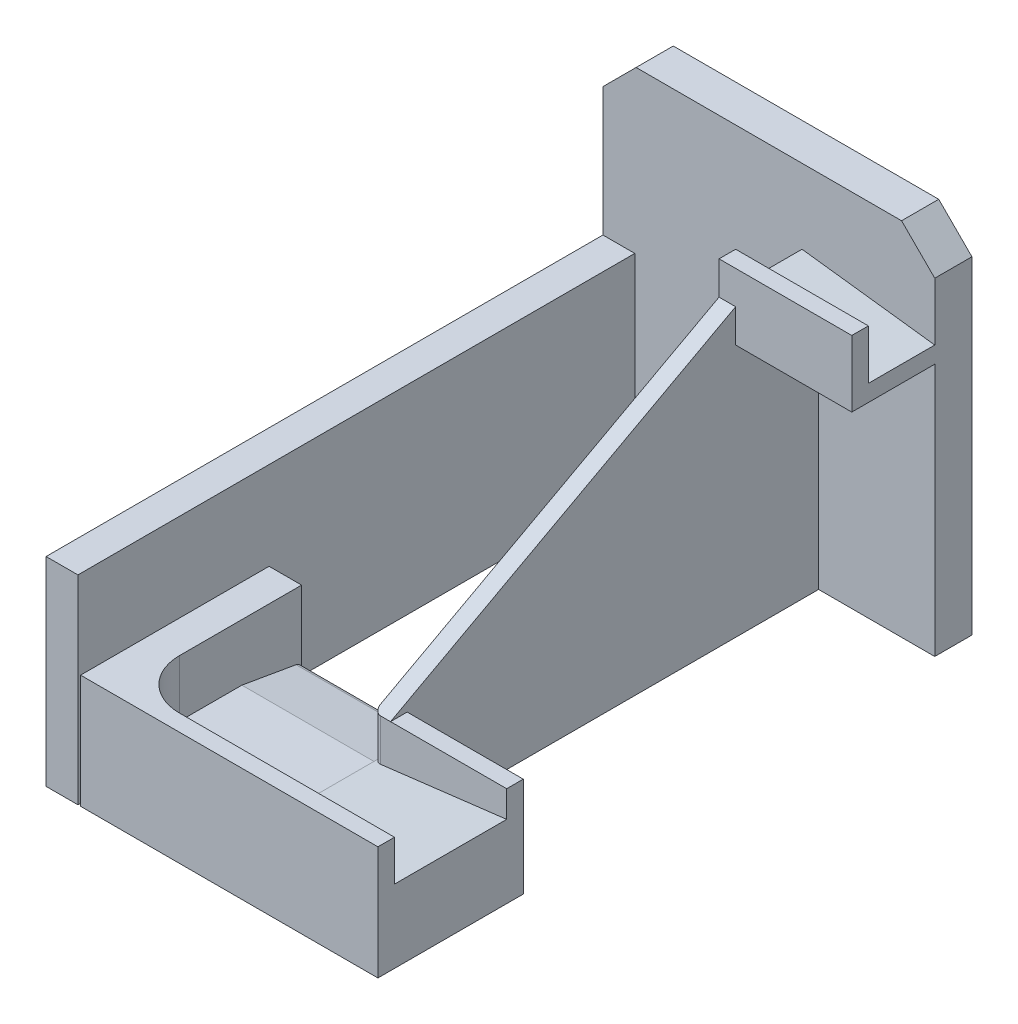
SolidWorks part; units mm, degrees
ref_plane "前视基准面" through (0, 0, 0) normal (0, 0, 1) x (1, 0, 0)
ref_plane "上视基准面" through (0, 0, 0) normal (0, 1, 0) x (1, 0, 0)
ref_plane "右视基准面" through (0, 0, 0) normal (1, 0, 0) x (0, 0, -1)
sketch "草图1" plane through (0, 0, 0) normal (0, 0, 1) x (1, 0, 0)
  line L0 (0, 49.365) -> (5, 54.365)
  line L1 (0, 0) -> (50, 0)
  line L2 (0, 0) -> (0, 49.365)
  line L3 (5, 54.365) -> (45, 54.365)
  line L4 (50, 0) -> (50, 49.365)
  line L5 (45, 54.365) -> (50, 49.365)
  point P1 (50, 54.365)
  point P2 (0, 54.365)
  dimension "D1" = 50
  dimension "D2" = 54.365
extrude "凸台-拉伸1" add sketch "草图1" along normal blind 5.6
ref_plane "基准面1" through (0, 0, 15.6) normal (0, 0, 1) x (1, 0, 0)
sketch "草图3" plane through (0, 0, 15.6) normal (0, 0, 1) x (1, 0, 0)
  line L0 (50, 0) -> (50, 49.365) construction
  line L1 (50, 38.145) -> (30, 38.145)
  line L2 (50, 38.145) -> (50, 48.145)
  line L3 (50, 48.145) -> (30, 48.145)
  line L4 (30, 38.145) -> (30, 48.145)
  line L5 (0, 0) -> (50, 0) construction
  dimension "D1" = 20
  dimension "D2" = 10
  dimension "D3" = 48.145
extrude "凸台-拉伸2" add sketch "草图3" along normal blind 2.5 separate body
sketch "草图5" plane through (0, 0, 15.6) normal (0, 0, -1) x (-1, 0, 0)
  line L0 (-30, 43.145) -> (-50, 40.645)
  line L1 (-30, 48.145) -> (-30, 38.145) construction
  line L2 (-50, 38.145) -> (-50, 48.145) construction
  line L3 (-30, 43.145) -> (-30, 38.145)
  line L4 (-30, 38.145) -> (-50, 38.145)
  line L5 (-50, 38.145) -> (-50, 40.645)
  dimension "D1" = 5
  dimension "D2" = 2.5
extrude "凸台-拉伸3" add sketch "草图5" along normal up to next
sketch "草图6" plane through (30, 0, 0) normal (-1, 0, 0) x (0, 0, 1)
  line L0 (18.1, 43.145) -> (70.1, 15)
  line L1 (18.1, 48.145) -> (18.1, 38.145) construction
  line L2 (70.1, 15) -> (70.1, 0)
  line L3 (70.1, 0) -> (5.6, 0)
  line L4 (18.1, 38.145) -> (18.1, 43.145)
  line L5 (18.1, 38.145) -> (5.6, 38.145)
  line L6 (5.6, 38.145) -> (5.6, 0)
  point P4 (37.716, 0)
  point P12 (6.4347, 0)
  dimension "D1" = 15
  dimension "D2" = 64.5
extrude "凸台-拉伸4" add sketch "草图6" against normal blind 2.5
ref_plane "基准面2" through (5.2, 0, 0) normal (-1, 0, 0) x (0, 0, 1)
sketch "草图7" plane through (5.2, 0, 0) normal (-1, 0, 0) x (0, 0, 1)
  line L0 (5.6, 0) -> (70.1, 0) construction
  line L1 (61.1, 0) -> (89.5, 0)
  line L2 (61.1, 0) -> (61.1, 17.12)
  line L3 (61.1, 17.12) -> (89.5, 17.12)
  line L4 (89.5, 0) -> (89.5, 17.12)
  dimension "D1" = 28.4
  dimension "D2" = 17.12
  dimension "D3" = 61.1
extrude "凸台-拉伸5" add sketch "草图7" against normal blind 4.9 separate body
sketch "草图8" plane through (0, 0, 89.5) normal (0, 0, 1) x (1, 0, 0)
  line L0 (50, 0) -> (50, 38.145) construction
  line L1 (10.1, 0) -> (50, 0)
  line L2 (10.1, 0) -> (10.1, 17.12)
  line L3 (10.1, 17.12) -> (50, 17.12)
  line L4 (50, 0) -> (50, 17.12)
  line L8 (10.1, 17.12) -> (5.2, 17.12) construction
extrude "凸台-拉伸6" add sketch "草图8" against normal blind 2.5
sketch "草图9" plane through (0, 0, 70.1) normal (0, 0, 1) x (1, 0, 0)
  line L0 (32.5, 15) -> (30, 15) construction
  line L1 (32.5, 0) -> (50, 0)
  line L2 (32.5, 0) -> (32.5, 15)
  line L3 (32.5, 15) -> (50, 15)
  line L4 (50, 0) -> (50, 15)
  line L8 (50, 0) -> (50, 17.12) construction
extrude "凸台-拉伸7" add sketch "草图9" against normal blind 2.5
sketch "草图11" plane through (10.1, 0, 0) normal (1, 0, 0) x (0, 0, -1)
  line L0 (-61.1, 0) -> (-61.1, 7)
  line L1 (-61.1, 17.12) -> (-61.1, 0) construction
  line L2 (-61.1, 7) -> (-70.1, 8.56)
  line L3 (-70.1, 8.56) -> (-87, 8.56)
  line L5 (-87, 0) -> (-87, 17.12) construction
  line L6 (-87, 8.56) -> (-87, 0)
  line L7 (-87, 0) -> (-61.1, 0)
  point P6 (0, 0)
  dimension "D1" = 7
  dimension "D2" = 9
extrude "凸台-拉伸8" add sketch "草图11" along normal up to surface (19.9 mm away) up to face at (30, 30.0906, 27.35)
fillet "圆角1" radius 1 1 edges at (20.05, 7, 61.1)
sketch "草图12" plane through (0, 0, 70.1) normal (0, 0, 1) x (1, 0, 0)
  line L0 (30, 0) -> (30, 8.56)
  line L1 (30, 8.56) -> (50, 11)
  line L2 (50, 0) -> (50, 15) construction
  line L3 (50, 11) -> (50, 0)
  line L4 (50, 0) -> (30, 0)
  point P4 (0, 0)
  point P10 (0, 0)
  point P12 (0, 0)
  dimension "D1" = 11
extrude "凸台-拉伸9" add sketch "草图12" along normal up to next
sketch "草图14" plane through (0, 0, 5.6) normal (0, 0, 1) x (1, 0, 0)
  line L0 (0, 0) -> (30, 0) construction
  line L1 (0, 0) -> (4.8, 0)
  line L2 (0, 0) -> (0, 30)
  line L3 (0, 30) -> (4.8, 30)
  line L4 (4.8, 0) -> (4.8, 30)
  point P5 (2.7232, 0)
  point P9 (0, 0)
  dimension "D1" = 4.8
  dimension "D2" = 30
extrude "凸台-拉伸12" add sketch "草图14" along normal up to surface (83.9 mm away) up to face at (27.6, 8.56, 89.5)
sketch "草图15" plane through (0, 8.56, 0) normal (0, 1, 0) x (1, 0, 0)
  line L0 (10.1, -70.1) -> (10.1, -87) construction
  line L1 (50, -87) -> (10.1, -87) construction
  line L2 (10.1, -79.5) -> (10.1, -87)
  line L3 (10.1, -87) -> (17.6, -87)
  arc A0 (10.1, -79.5) -> (17.6, -87) centre (17.6, -79.5) ccw
  dimension "D1" = 7.5
extrude "凸台-拉伸13" add sketch "草图15" along normal up to surface (8.56 mm away) up to face at (21.7667, 17.12, 79.2)
fillet "圆角3" radius 1 1 edges at (30, 11.78, 70.1)
